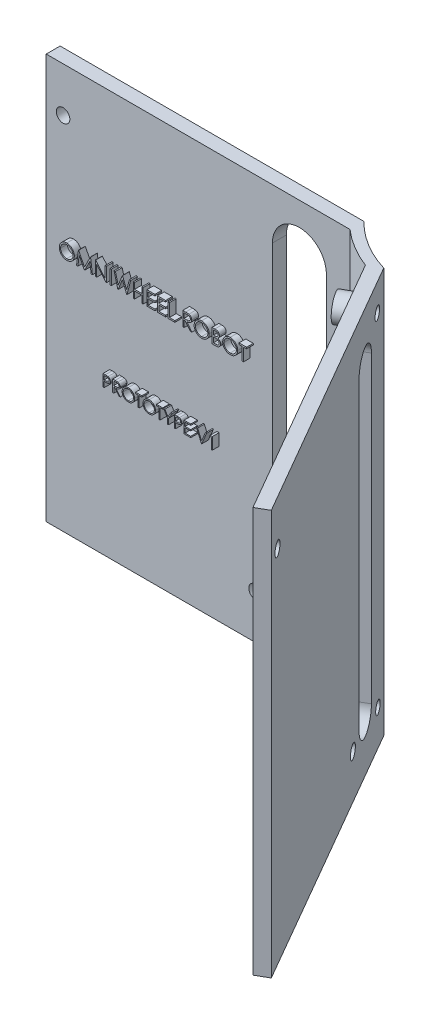
SolidWorks part; units mm, degrees
ref_plane "Plan de face" through (0, 0, 0) normal (0, 0, 1) x (1, 0, 0)
ref_plane "Plan de dessus" through (0, 0, 0) normal (0, 1, 0) x (1, 0, 0)
ref_plane "Plan de droite" through (0, 0, 0) normal (1, 0, 0) x (0, 0, -1)
sketch "Esquisse3" plane through (0, 0, 0) normal (0, 1, 0) x (1, 0, 0)
  line L0 (-150.1573, 0) -> (189.6273, 0) construction
  line L1 (-83.8395, -145.9242) -> (87.7229, 151.2306) construction
  line L2 (-78.0725, 135.2255) -> (117.7517, -203.9519) construction
  line L3 (-125, 131.2995) -> (-125, -153.5705) construction
  line L4 (-25, -24.4949) -> (-115, -24.4949)
  line L6 (-21.2883, 25.5051) -> (-23.9685, 25.5051)
  line L7 (-115, -24.4949) -> (-115, 25.5051)
  line L8 (-25, -24.4949) -> (-115, 25.5051) construction
  line L9 (-21.2883, 25.5051) -> (-115, -24.4949) construction
  line L10 (-23.9685, 25.5051) -> (-115, 25.5051)
  line L11 (34.0723, 8.0048) -> (79.5881, 86.8404)
  line L12 (36.2868, 111.8404) -> (79.5881, 86.8404)
  line L13 (-8.7132, 33.8981) -> (36.2868, 111.8404)
  line L14 (-10.1038, -33.5099) -> (35.4119, -112.3455)
  line L15 (78.7132, -87.3455) -> (35.4119, -112.3455)
  line L16 (33.7132, -9.4032) -> (78.7132, -87.3455)
  line L17 (-23.9685, 25.5051) -> (-25, -24.4949)
  line L18 (-8.7132, 33.8981) -> (34.0723, 8.0048)
  line L19 (-10.1038, -33.5099) -> (33.7132, -9.4032)
  line L20 (-25, -28.6182) -> (-115, -28.6182)
  line L21 (-115, -28.6182) -> (-115, -24.4949)
  line L22 (-13.5526, -35.5011) -> (31.9631, -114.3367)
  line L23 (31.9631, -114.3367) -> (35.4119, -112.3455)
  circle A0 centre (0, 0) radius 125
  circle A1 centre (0, 0) radius 35
  circle A2 centre (0, 0) radius 125
  circle A3 centre (0, 0) radius 125
  circle A4 centre (0, 0) radius 38
  point P9 (-69.0908, 0)
  point P32 (0, 0)
  dimension "D1" = 250
  dimension "D4" = 70
  dimension "D2" = 120
  dimension "D3" = 120
  dimension "D5" = 10
  dimension "D6" = 50
  dimension "D7" = 90
  dimension "D9" = 3
  dimension "D8" = 3
extrude "Boss.-Extru.1" add sketch "Esquisse3" along normal blind 120 contours A4 L4 L21 L20 | L4 A4 L14 A1 | A4 L22 L23 L14 region at (-18.6168, 0, 30.8794) region at (-71.0566, 0, 26.5723) region at (11.4638, 0, 74.8797)
sketch "Esquisse4" plane through (0, 0, 28.6182) normal (0, 0, 1) x (1, 0, 0)
  line L0 (-40, 120) -> (-40, 0) construction
  line L1 (-25, 120) -> (-115, 120) construction
  line L2 (-25, 0) -> (-115, 0) construction
  line L3 (-48, 105) -> (-48, 15)
  line L4 (-25, 120) -> (-25, 0) construction
  line L5 (-115, 60) -> (-20.315, 60) construction
  line L6 (-115, 120) -> (-115, 0) construction
  line L7 (-32, 105) -> (-32, 15)
  arc A0 (-48, 15) -> (-32, 15) centre (-40, 15) ccw
  arc A1 (-48, 105) -> (-32, 105) centre (-40, 105) cw
  dimension "D1" = 8
  dimension "D2" = 15
  dimension "D3" = 45
  dimension "D4" = 45
extrude "Enlèv. mat.-Extru.1" cut sketch "Esquisse4" against normal through all
sketch "Esquisse5" plane through (-25.5369, 0, 14.7437) normal (-0.866, 0, 0.5) x (0.5, 0, 0.866)
  line L0 (38.9685, 120) -> (38.9685, 0) construction
  line L1 (23.9685, 120) -> (115, 120) construction
  line L2 (43.9685, 105) -> (43.9685, 15)
  line L3 (38.9685, 60) -> (127.8483, 60) construction
  line L4 (115, 120) -> (115, 0) construction
  line L5 (23.9685, 120) -> (23.9685, 0) construction
  line L6 (33.9685, 105) -> (33.9685, 15)
  arc A0 (43.9685, 15) -> (33.9685, 15) centre (38.9685, 15) cw
  arc A1 (43.9685, 105) -> (33.9685, 105) centre (38.9685, 105) ccw
  point P14 (115, 60)
  dimension "D1" = 5
  dimension "D2" = 45
  dimension "D3" = 45
  dimension "D4" = 15
extrude "Enlèv. mat.-Extru.2" cut sketch "Esquisse5" against normal through all
sketch "Esquisse6" plane through (0, 0, 28.6182) normal (0, 0, 1) x (1, 0, 0)
  circle A0 centre (-110, 106.75) radius 2 construction
  circle A1 centre (-110, 106.75) radius 2
sketch "Esquisse7" plane through (-25.5369, 0, 14.7437) normal (-0.866, 0, 0.5) x (0.5, 0, 0.866)
  circle A0 centre (110, 106.75) radius 2 construction
  circle A1 centre (110, 106.75) radius 2
extrude "Enlèv. mat.-Extru.3" cut sketch "Esquisse6" against normal through all
extrude "Enlèv. mat.-Extru.4" cut sketch "Esquisse7" against normal through all
sketch "Esquisse8" plane through (0, 0, 28.6182) normal (0, 0, 1) x (1, 0, 0)
  line L0 (-115, 72.2203) -> (-48, 72.2203) construction
  line L1 (-107.7615, 44.975) -> (-51.4576, 44.975) construction
  line L2 (-115, 120) -> (-115, 0) construction
  line L3 (-48, 105) -> (-48, 15) construction
  text T0 "OMNIWHEEL ROBOT" font "Century Gothic" height in points 16
  text T1 "PROTOTYPE V1" font "Century Gothic" height 3.5
extrude "Boss.-Extru.2" add sketch "Esquisse8" along normal blind 2
sketch "Esquisse9" plane through (0, 0, 28.6182) normal (0, 0, 1) x (1, 0, 0)
  circle A0 centre (-53, 13) radius 2 construction
  circle A1 centre (-53, 13) radius 2
sketch "Esquisse10" plane through (-25.5369, 0, 14.7437) normal (-0.866, 0, 0.5) x (0.5, 0, 0.866)
  circle A0 centre (48.9685, 13) radius 2 construction
  circle A1 centre (48.9685, 13) radius 2
extrude "Enlèv. mat.-Extru.5" cut sketch "Esquisse9" against normal through all
extrude "Enlèv. mat.-Extru.6" cut sketch "Esquisse10" against normal through all
sketch "Esquisse11" plane through (-25.5369, 0, 14.7437) normal (-0.866, 0, 0.5) x (0.5, 0, 0.866)
  circle A2 centre (28.7064, 10.4795) radius 1.8028
  circle A3 centre (29.2064, 111.9795) radius 1.8028
  circle A4 centre (29.2064, 111.9795) radius 3.8028
  circle A5 centre (28.7064, 10.4795) radius 3.8028
  dimension "D1" = 2
extrude "Boss.-Extru.3" add sketch "Esquisse11" along normal blind 5 contours A2 | A4 | A5 | A3 region at (-11.1837, 10.4795, 39.6042)
sketch "Esquisse12" plane through (-25.5369, 0, 14.7437) normal (-0.866, 0, 0.5) x (0.5, 0, 0.866)
  circle A0 centre (29.2064, 111.9795) radius 1.8028 construction
  circle A1 centre (29.2064, 111.9795) radius 1.8028
  circle A2 centre (28.7064, 10.4795) radius 1.8028 construction
  circle A3 centre (28.7064, 10.4795) radius 1.8028
extrude "Enlèv. mat.-Extru.7" cut sketch "Esquisse12" against normal up to next
